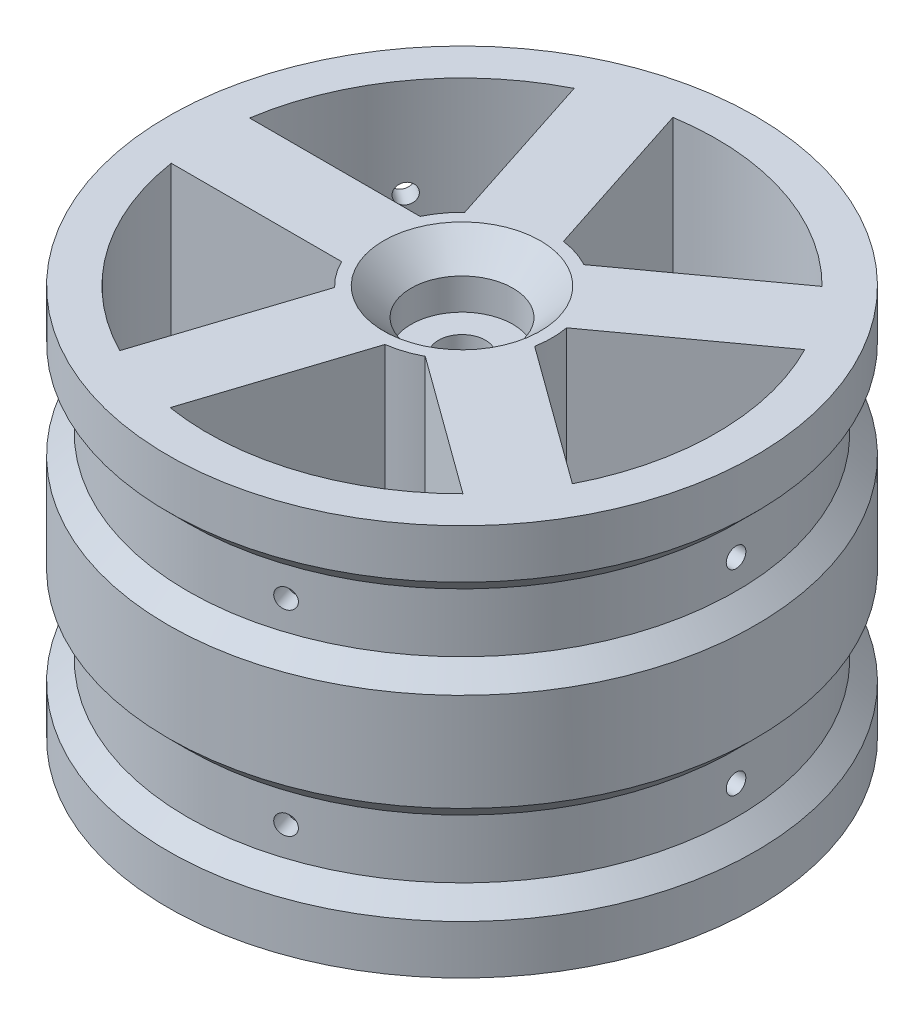
SolidWorks part; units mm, degrees
material "ABS"
ref_plane "Front Plane" through (0, 0, 0) normal (0, 0, 1) x (1, 0, 0)
ref_plane "Top Plane" through (0, 0, 0) normal (0, 1, 0) x (1, 0, 0)
ref_plane "Right Plane" through (0, 0, 0) normal (1, 0, 0) x (0, 0, -1)
sketch "Sketch1" plane through (0, 0, 0) normal (0, 0, 1) x (1, 0, 0)
  line L0 (0, 0) -> (75, 0) construction
  line L1 (0, 0) -> (0, 50) construction
  line L2 (6, -35) -> (6, 35)
  line L3 (6, 35) -> (13, 35)
  line L4 (13, 35) -> (13, 43)
  line L5 (13, 43) -> (20, 50)
  line L6 (20, 50) -> (75, 50)
  line L7 (75, 50) -> (75, 32.5)
  line L8 (20, -50) -> (75, -50)
  line L9 (6, -35) -> (13, -35)
  line L10 (13, -35) -> (13, -43)
  line L11 (13, -43) -> (20, -50)
  line L12 (75, 17.5) -> (70, 17.5)
  line L13 (70, 17.5) -> (70, 32.5)
  line L14 (70, 32.5) -> (75, 32.5)
  line L15 (75, 17.5) -> (75, -17.5)
  line L16 (75, -17.5) -> (75, 50)
  line L17 (70, -32.5) -> (75, -32.5)
  line L18 (70, -17.5) -> (70, -32.5)
  line L19 (75, -17.5) -> (70, -17.5)
  line L20 (75, -50) -> (75, -32.5)
  line L21 (75, -32.5) -> (75, -50)
  point P13 (6, 0)
  point P17 (70, 25)
  dimension "D1" = 75
  dimension "D3" = 6
  dimension "D2" = 50
  dimension "D4" = 35
  dimension "D5" = 8
  dimension "D6" = 26
  dimension "D7" = 45
  dimension "D8" = 5
  dimension "D9" = 15
  dimension "D10" = 25
revolve "Revolve1" add sketch "Sketch1" angle 360 about L1 region at (40.9534, 0, 0)
ref_axis "Axis1" through (0, 55, 0) along (0, -1, 0)
chamfer "Chamfer1" distance 5 angle 45 4 edges at (0, -32.5, -75) (0, -17.5, -75) (0, 32.5, -75) (0, 17.5, -75)
sketch "Sketch2" plane through (0, 0, 0) normal (0, 1, 0) x (1, 0, 0)
  line L0 (0, 0) -> (52.5861, 38.206) construction
  line L1 (-55, 0) -> (55, 0) construction
  line L2 (0, 0) -> (52.5861, -38.206) construction
  line L3 (22.6345, -4.0842) -> (57.8379, -29.661)
  line L4 (22.6345, 4.0842) -> (57.8379, 29.661)
  line L5 (17.013, 0) -> (58.464, 30.1159) construction
  line L6 (17.013, 0) -> (58.464, -30.1159) construction
  circle A0 centre (0, 0) radius 13 construction
  circle A1 centre (0, 0) radius 13 construction
  circle A2 centre (0, 0) radius 23
  circle A3 centre (0, 0) radius 75 construction
  circle A4 centre (0, 0) radius 75 construction
  circle A5 centre (0, 0) radius 65
  dimension "D3" = 36
  dimension "D1" = 10
  dimension "D2" = 10
  dimension "D4" = 10
extrude "Cut-Extrude1" cut sketch "Sketch2" against normal through all both and the other way through all contours L3 A5 L4 A2 region at (47.8327, 0, 0)
pattern_circular "CirPattern1" count 5 over 360 about axis through (0, 55, 0) along (0, -1, 0) of "Cut-Extrude1"
sketch "Sketch3" plane through (0, 0, 0) normal (1, 0, 0) x (0, 0, -1)
  line L0 (0, 0) -> (0, 25) construction
  line L1 (0, 55) -> (0, -55) construction
  line L2 (82.5, 0) -> (-82.5, 0) construction
  circle A0 centre (0, 25) radius 2.5
  circle A1 centre (0, -25) radius 2.5
  dimension "D2" = 5
  dimension "D1" = 25
extrude "Cut-Extrude2" cut sketch "Sketch3" along normal through all from offset 50
pattern_circular "CirPattern2" count 5 over 360 about axis through (0, 55, 0) along (0, -1, 0) of "Cut-Extrude2"
equation "\"D1@Sketch1\"=\"dia\"/2"
equation "\"dia\"= 150"
equation "\"width\"= 100"
equation "\"D2@Sketch1\"=\"width\"/2"
equation "\"center_width\" = 70"
equation "\"D4@Sketch1\"=\"center_width\"/2"
